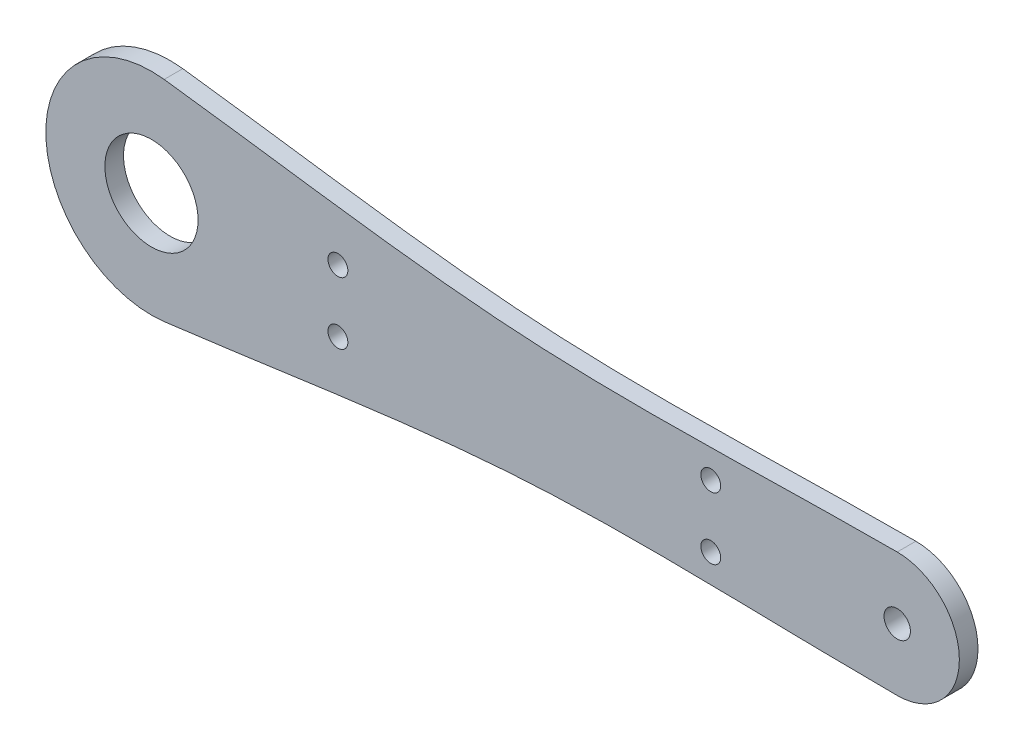
SolidWorks part; units mm, degrees
ref_plane "Front Plane" through (0, 0, 0) normal (0, 0, 1) x (1, 0, 0)
ref_plane "Top Plane" through (0, 0, 0) normal (0, 1, 0) x (1, 0, 0)
ref_plane "Right Plane" through (0, 0, 0) normal (1, 0, 0) x (0, 0, -1)
sketch "Sketch1" plane through (0, 0, 0) normal (0, 0, 1) x (1, 0, 0)
  line L0 (-103.1351, 0) -> (103.1351, 0) construction
  line L3 (0, 10) -> (0, -10) construction
  circle A2 centre (-60, 0) radius 7.5
  circle A3 centre (60, 0) radius 2.125
  arc A4 (-57.9568, 16.8768) -> (-57.9568, -16.8768) centre (-60, 0) ccw
  arc A5 (60, -10) -> (60, 10) centre (60, 0) ccw
  circle A6 centre (-30, 5) radius 1.6
  circle A7 centre (30, 5) radius 1.6
  circle A8 centre (30, -5) radius 1.6
  circle A9 centre (-30, -5) radius 1.6
  spline S0 degree 3 poles (60, 10) (39.9383, 10) (0.416, 7.6936) (-38.5985, 14.4869) (-57.9568, 16.8768) knots 0 0 0 0 0.506914 1 1 1 1
  spline S1 degree 3 poles (60, -10) (39.9383, -10) (0.416, -7.6936) (-38.5985, -14.4869) (-57.9568, -16.8768) knots 0 0 0 0 0.506914 1 1 1 1
  point P7 (0, 0)
  dimension "D3" = 15
  dimension "D1" = 4.25
  dimension "D2" = 34
  dimension "D4" = 20
  dimension "D10" = 3.2
  dimension "D5" = 120
  dimension "D6" = 20
  dimension "D7" = 60
  dimension "D8" = 30
  dimension "D9" = 5
  dimension "D14" = 30
  dimension "D15" = 5
  dimension "D12" = 2
  dimension "D13" = 2
extrude "Boss-Extrude1" add sketch "Sketch1" along normal blind 3
equation "\"L1\"= 120mm'Upper arm"
equation "\"L3\"= 75mm'Wrist→TCP"
equation "\"h0\"= 75mm'Shoulder height"
equation "\"t_link\"= 3mm'Link plate thickness"
equation "\"t_bracket\"= 4mm'Bracket thickness"
equation "\"d_pin\"= 4mm'Pin diameter (M4)"
equation "\"c_fit\"= 0.2mm'Nominal clearance - measured PLA 2026-10-01"
equation "\"L2\"= 120mm'Forearm"
equation "\"c_fit_pivot\"= \"c_fit\" + 0.05mm'Gripper pivot clearance - chosen 0.25 mm 2026-10-01"
equation "\"d_pin_gripper\"= 3mm'Gripper pivot diameter"
equation "\"w_link\"= 20mm'Link plate depth (bending direction)"
equation "\"w_gap\"= 20mm'Twin-plate gap - provisional, set by elbow servo mount"
equation "\"D1@Boss-Extrude1\"=\"t_link\""
equation "\"d_boss\"= 13mm'MG996R output boss dia - from downloaded model, verify with calipers"
equation "\"c_boss\"= 1mm'Radial clearance around servo boss"
equation "\"d_servo_hole\"= \"d_boss\" + 2 * \"c_boss\"'Plate clearance hole for servo boss (15 mm)"
equation "\"t_rim\"= 9.5mm'Min material around servo hole (M3 hole + 3 mm webs each side)"
equation "\"w_link_end\"= \"d_servo_hole\" + 2 * \"t_rim\"'Link plate end width at servo end (34 mm)"
equation "\"d_hole_m3\"= \"d_pin_gripper\" + \"c_fit\"'M3 bolt clearance hole (spacer and adapter bolts)"
equation "\"d_hole_pivot\"= \"d_pin\" + \"c_fit_pivot\"'M4 pivot hole where the pin rotates (4.25 mm)"
equation "\"D3@Sketch1\"=\"d_servo_hole\""
equation "\"D1@Sketch1\"=\"d_pin\"+\"c_fit_pivot\""
equation "\"D2@Sketch1\"=\"w_link_end\""
equation "\"D4@Sketch1\"=\"w_link\""
equation "\"D5@Sketch1\"=\"L1\""
equation "\"D6@Sketch1\"=\"w_link\""
equation "\"D10@Sketch1\"=\"d_hole_m3\""
